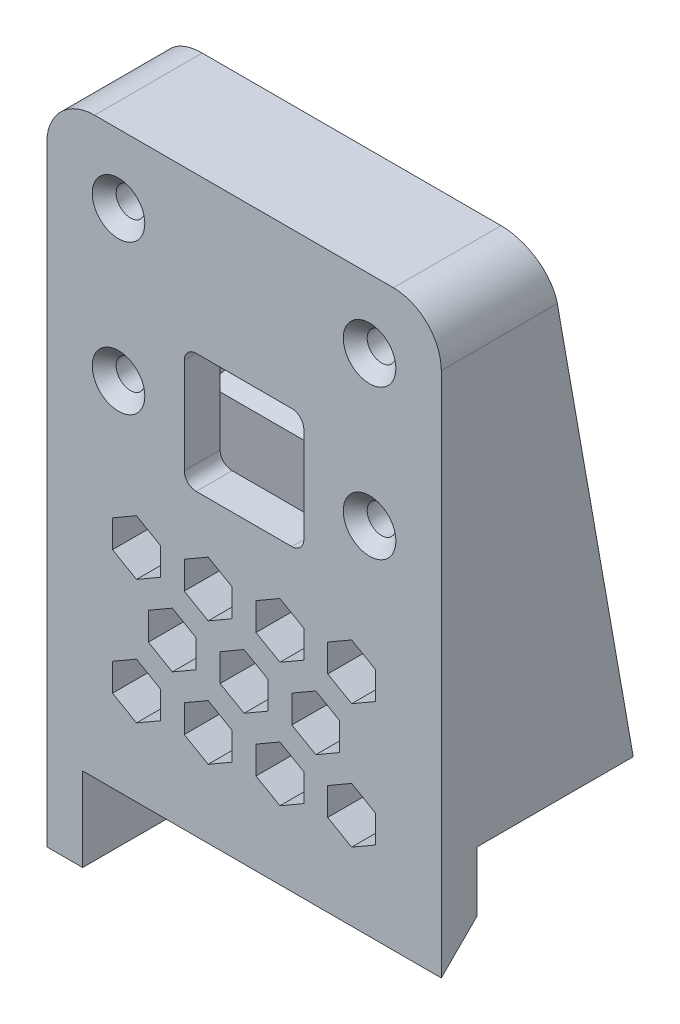
SolidWorks part; units mm, degrees
material "ABS PC"
ref_plane "Front Plane" through (0, 0, 0) normal (0, 0, 1) x (1, 0, 0)
ref_plane "Top Plane" through (0, 0, 0) normal (0, 1, 0) x (1, 0, 0)
ref_plane "Right Plane" through (0, 0, 0) normal (1, 0, 0) x (0, 0, -1)
sketch "Sketch1" plane through (0, 0, 0) normal (0, 0, 1) x (1, 0, 0)
  line L1 (16.5, -20) -> (-16.5, -20)
  line L2 (16.5, -20) -> (16.5, 20)
  line L3 (16.5, 20) -> (-16.5, 20)
  line L4 (-16.5, -20) -> (-16.5, 20)
  line L5 (16.5, -20) -> (-16.5, 20) construction
  line L6 (16.5, 20) -> (-16.5, -20) construction
  point P0 (0, 0)
  dimension "D1" = 33
  dimension "D2" = 40
extrude "Boss-Extrude1" add sketch "Sketch1" against normal blind 3
sketch "Sketch2" plane through (0, 0, -3) normal (0, 0, -1) x (-1, 0, 0)
  line L9 (13.5, -17) -> (13.5, 17)
  line L10 (13.5, 17) -> (-13.5, 17)
  line L11 (-13.5, 17) -> (-13.5, -17)
  line L12 (-13.5, -17) -> (13.5, -17)
  line L13 (13.5, -17) -> (13.5, 17)
  line L14 (13.5, 17) -> (-13.5, 17)
  line L15 (-13.5, 17) -> (-13.5, -17)
  line L16 (-13.5, -17) -> (13.5, -17)
  line L22 (16.5, -20) -> (16.5, 20)
  line L23 (16.5, 20) -> (-16.5, 20)
  line L24 (-16.5, 20) -> (-16.5, -20)
  line L25 (-16.5, -20) -> (16.5, -20)
  line L26 (16.5, -20) -> (16.5, 20)
  line L27 (16.5, 20) -> (-16.5, 20)
  line L28 (-16.5, 20) -> (-16.5, -20)
  line L29 (-16.5, -20) -> (16.5, -20)
  dimension "D1" = 3
  dimension "D2" = 0
extrude "Boss-Extrude2" add sketch "Sketch2" along normal blind 3
sketch "Sketch3" plane through (0, 0, 0) normal (0, 0, 1) x (1, 0, 0)
  line L0 (0, -20) -> (0, 2) construction
  line L1 (-16.5, -20) -> (16.5, -20) construction
  line L3 (-5, -3) -> (5, -3)
  line L4 (-5, -3) -> (-5, 7)
  line L5 (-5, 7) -> (5, 7)
  line L6 (5, -3) -> (5, 7)
  line L7 (-5, -3) -> (5, 7) construction
  line L8 (-5, 7) -> (5, -3) construction
  dimension "D1" = 10
  dimension "D2" = 22
extrude "Cut-Extrude1" cut sketch "Sketch3" against normal blind 3
hole_wizard "CSK for M2 Flat Head Machine Screw1" positions "Sketch9" profile "Sketch10" countersink size "M2" standard "ANSI Metric"
sketch "Sketch9" plane through (0, 0, 0) normal (0, 0, 1) x (1, 0, 0)
  line L0 (0, 0) -> (0, 8) construction
  line L3 (-10.5, 1.75) -> (10.5, 1.75)
  line L4 (-10.5, 1.75) -> (-10.5, 14.25)
  line L5 (-10.5, 14.25) -> (10.5, 14.25)
  line L6 (10.5, 1.75) -> (10.5, 14.25)
  line L7 (-10.5, 1.75) -> (10.5, 14.25) construction
  line L8 (-10.5, 14.25) -> (10.5, 1.75) construction
  point P5 (10.5, 14.25)
  point P8 (-10.5, 1.75)
  point P9 (-10.5, 14.25)
  point P10 (10.5, 1.75)
  dimension "D1" = 12.5
  dimension "D2" = 21
  dimension "D3" = 8
sketch "Sketch10" plane through (10.5, 1.75, 0) normal (1, 0, 0) x (0, -1, 0)
  line L0 (0, 0) -> (0, 5.721)
  line L1 (0, 5.721) -> (1.2, 5)
  line L2 (1.2, 5) -> (1.2, 1)
  line L3 (1.2, 1) -> (2.2, 0)
  line L5 (2.2, 0) -> (0, 0)
  line L6 (-1.2, 1) -> (-2.2, 0) construction
  line L10 (0, 5.721) -> (-1.2, 5) construction
  line L11 (0, -6.35) -> (0, 107.95) construction
  dimension "Hole Dia." = 2.4
  dimension "Hole Depth" = 5
  dimension "Near C'Sink Dia." = 4.4
  dimension "Near C'Sink Angle" = 90
  dimension "Drill Angle" = 118
sketch "Sketch11" plane through (-16.5, 0, 0) normal (-1, 0, 0) x (0, 0, 1)
  line L0 (-6, 20) -> (-9, 20)
  line L1 (-9, 20) -> (-16.0531, -20)
  line L2 (-16.0531, -20) -> (-6, -20)
  line L4 (-6, -20) -> (-6, 20)
  dimension "D1" = 3
  dimension "D2" = 10
extrude "Boss-Extrude4" add sketch "Sketch11" against normal blind 3
hole_wizard "Ø3.5 (3.5) Diameter Hole1" [suppressed] positions "Sketch12" profile "Sketch13" hole size "Ø3.5" standard "ANSI Metric"
sketch "Sketch12" plane through (-16.5, 0, 0) normal (-1, 0, 0) x (0, 0, 1)
  line L0 (-8.0249, -7.4838) -> (-8.9122, -12.5162) construction
  line L2 (-8, 20) -> (-15.0531, -20) construction
  line L3 (-12.4686, -10) -> (-8.4686, -10) construction
  line L4 (-15.0531, -20) -> (0, -20) construction
  point P0 (-8.0249, -7.4838)
  point P1 (-8.9122, -12.5162)
  dimension "D1" = 5.11
  dimension "D2" = 4
  dimension "D3" = 10
sketch "Sketch13" plane through (-16.5, -7.4838, -8.0249) normal (0, 1, 0) x (0, 0, 1)
  line L0 (0, 0) -> (0, 6.0515)
  line L1 (0, 6.0515) -> (1.75, 5)
  line L2 (1.75, 5) -> (1.75, 0)
  line L5 (1.75, 0) -> (0, 0)
  line L10 (0, 6.0515) -> (-1.75, 5) construction
  line L11 (0, -6.35) -> (0, 107.95) construction
  dimension "Hole Dia." = 3.5
  dimension "Hole Depth" = 5
  dimension "Drill Angle" = 118
mirror "Mirror1" about plane through (0, 0, 0) normal (1, 0, 0) of "Boss-Extrude4"
fillet "Fillet1" radius 1 4 edges at (-5, -3, -1.5) (5, -3, -1.5) (-5, 7, -1.5) (5, 7, -1.5)
sketch "Sketch15" plane through (0, 0, -6) normal (0, 0, -1) x (-1, 0, 0)
  line L1 (-13.5, 17) -> (13.5, 17)
  line L2 (-13.5, 17) -> (-13.5, 20)
  line L3 (-13.5, 20) -> (13.5, 20)
  line L4 (13.5, 17) -> (13.5, 20)
extrude "Boss-Extrude5" add sketch "Sketch15" along normal up to surface (3.529 mm away) up to face at (15, 0, -12.5265)
sketch "Sketch16" plane through (0, -20, 0) normal (0, -1, 0) x (1, 0, 0)
  line L0 (13.5, -9.529) -> (13.5, -3) construction
  line L1 (-13.5, -6) -> (13.5, -6)
  line L2 (-13.5, -6) -> (-13.5, -3)
  line L3 (-13.5, -3) -> (13.5, -3)
  line L4 (13.5, -6) -> (13.5, -3)
  line L5 (13.5, -6) -> (-13.5, -6) construction
  line L6 (-16.5, 0) -> (16.5, 0) construction
  dimension "D1" = 3
extrude "Cut-Extrude6" cut sketch "Sketch16" against normal blind 3 contours L3 L4 L1 L2
sketch "Sketch17" [suppressed] plane through (16.5, 0, 0) normal (1, 0, 0) x (0, 0, -1)
  line L0 (8.0249, -7.4838) -> (8.9122, -12.5162) construction
  circle A0 centre (8.4686, -10) radius 3
  dimension "D1" = 6
extrude "Cut-Extrude7" [suppressed] cut sketch "Sketch17" against normal blind 3
sketch "Sketch18" plane through (0, 2.1422, -12.1488) normal (0, 0.1736, -0.9848) x (-1, 0, 0)
  line L0 (13.5, 15.087) -> (-13.5, 15.087) construction
  line L1 (-13.5, -16.913) -> (13.5, -16.913)
  line L2 (-13.5, -16.913) -> (-13.5, -6.913)
  line L3 (-13.5, -6.913) -> (13.5, -6.913)
  line L4 (13.5, -16.913) -> (13.5, -6.913)
  line L7 (-13.5, 15.087) -> (-13.5, -22.4837) construction
  line L8 (13.5, 15.087) -> (13.5, -22.4837) construction
  dimension "D1" = 10
  dimension "D2" = 22
extrude "Boss-Extrude6" add sketch "Sketch18" against normal blind 3
sketch "Sketch19" plane through (0, 0, 0) normal (0, 0, 1) x (1, 0, 0)
  line L1 (-16.5, -20) -> (16.5, -20)
  line L2 (-16.5, -20) -> (-16.5, -24.0275)
  line L3 (-16.5, -24.0275) -> (16.5, -24.0275)
  line L4 (16.5, -20) -> (16.5, -24.0275)
extrude "Cut-Extrude8" [suppressed] cut sketch "Sketch19" against normal through all
chamfer "Chamfer4" [suppressed] distance 2 angle 45
sketch "Sketch20" [suppressed] plane through (-16.5, 0, 0) normal (-1, 0, 0) x (0, 0, 1)
  line L0 (-8.0249, -7.4838) -> (-8.9122, -12.5162) construction
  line L1 (-8.9122, -12.5162) -> (-8.0249, -7.4838) construction
  line L2 (-10.6357, -12.2123) -> (-9.7483, -7.1799)
  line L3 (-7.1888, -12.8201) -> (-6.3015, -7.7877)
  arc A0 (-10.6357, -12.2123) -> (-7.1888, -12.8201) centre (-8.9122, -12.5162) ccw
  arc A1 (-6.3015, -7.7877) -> (-9.7483, -7.1799) centre (-8.0249, -7.4838) ccw
  circle A2 centre (-8.0249, -7.4838) radius 1.75 construction
  point P5 (-8.4686, -10)
extrude "Cut-Extrude9" [suppressed] cut sketch "Sketch20" against normal blind 3
fillet "Fillet2" radius 4 2 edges at (16.5, 20, -4.5) (-16.5, 20, -4.5)
fillet "Fillet3" radius 2 2 edges at (-13.5, 17, -6.2645) (13.5, 17, -6.2645)
sketch "Sketch21" plane through (-16.5, 0, 0) normal (-1, 0, 0) x (0, 0, 1)
  line L1 (-16.0531, -20) -> (0, -20)
  line L2 (-16.0531, -20) -> (-16.0531, -35)
  line L3 (-16.0531, -35) -> (0, -35)
  line L4 (0, -20) -> (0, -35)
  dimension "D1" = 15
extrude "Boss-Extrude7" add sketch "Sketch21" against normal up to surface (3 mm away) up to face at (-13.5, -6.1751, -10.362)
sketch "Sketch22" plane through (-16.5, 0, 0) normal (-1, 0, 0) x (0, 0, 1)
  line L0 (-8.0265, -29.555) -> (-8.0265, -24.445) construction
  line L1 (-9.5265, -29.555) -> (-9.5265, -24.445)
  line L2 (-6.5265, -29.555) -> (-6.5265, -24.445)
  line L3 (-8.0265, -29.555) -> (-8.0265, -35) construction
  line L4 (-16.0531, -35) -> (0, -35) construction
  arc A0 (-9.5265, -29.555) -> (-6.5265, -29.555) centre (-8.0265, -29.555) ccw
  arc A1 (-6.5265, -24.445) -> (-9.5265, -24.445) centre (-8.0265, -24.445) ccw
  point P2 (-8.0265, -27)
  dimension "D1" = 5.11
  dimension "D2" = 8
  dimension "D3" = 3
extrude "Cut-Extrude10" cut sketch "Sketch22" against normal blind 10
sketch "Sketch23" plane through (0, 0, 0) normal (0, 0, 1) x (1, 0, 0)
  line L1 (-13.5, -20) -> (16.5, -20)
  line L2 (-13.5, -20) -> (-13.5, -28)
  line L3 (-13.5, -28) -> (16.5, -28)
  line L4 (16.5, -20) -> (16.5, -28)
  dimension "D1" = 8
extrude "Boss-Extrude8" add sketch "Sketch23" against normal blind 3
chamfer "Chamfer5" distance 3 angle 45 1 edges at (1.5, -28, -3)
sketch "Sketch24" plane through (0, 0, 0) normal (0, 0, 1) x (1, 0, 0)
  line L0 (0, -10.5048) -> (0, -23.4952) construction
  line L1 (0, -10.5048) -> (-7.5, -23.4952)
  line L2 (-7.5, -23.4952) -> (7.5, -23.4952)
  line L3 (0, -10.5048) -> (7.5, -23.4952)
  point P6 (0, -17)
  dimension "D1" = 15
  dimension "D2" = 17
extrude "Cut-Extrude11" [suppressed] cut sketch "Sketch24" against normal blind 3
fillet "Fillet4" [suppressed] radius 2
chamfer "Chamfer6" distance 1 angle 45 4 edges at (-16.5, -27, -6.5265) (-16.5, -22.945, -8.0265) (-16.5, -31.055, -8.0265) (-16.5, -27, -9.5265)
sketch "Sketch25" plane through (0, 0, 0) normal (0, 0, 1) x (1, 0, 0)
  line L0 (0, -9.5695) -> (0, -22.3789) construction
  line L1 (-1, -8.4148) -> (-3, -7.2601)
  line L2 (-7, -8.4148) -> (-9, -7.2601)
  line L3 (-9, -7.2601) -> (-11, -8.4148)
  line L4 (-11, -8.4148) -> (-11, -10.7242)
  line L5 (-11, -10.7242) -> (-9, -11.8789)
  line L6 (-9, -11.8789) -> (-7, -10.7242)
  line L7 (-7, -10.7242) -> (-7, -8.4148)
  line L8 (-3, -7.2601) -> (-5, -8.4148)
  line L9 (-5, -8.4148) -> (-5, -10.7242)
  line L10 (-5, -10.7242) -> (-3, -11.8789)
  line L11 (-3, -11.8789) -> (-1, -10.7242)
  line L12 (-1, -10.7242) -> (-1, -8.4148)
  line L13 (1, -10.7242) -> (1, -8.4148)
  line L14 (3, -11.8789) -> (1, -10.7242)
  line L15 (5, -10.7242) -> (3, -11.8789)
  line L16 (5, -8.4148) -> (5, -10.7242)
  line L17 (3, -7.2601) -> (5, -8.4148)
  line L18 (7, -10.7242) -> (7, -8.4148)
  line L19 (9, -11.8789) -> (7, -10.7242)
  line L20 (11, -10.7242) -> (9, -11.8789)
  line L21 (11, -8.4148) -> (11, -10.7242)
  line L22 (9, -7.2601) -> (11, -8.4148)
  line L23 (7, -8.4148) -> (9, -7.2601)
  line L24 (1, -8.4148) -> (3, -7.2601)
  line L25 (-3, -9.5695) -> (-9, -9.5695) construction
  line L26 (0, -12.4563) -> (-2, -13.611)
  line L27 (-6, -12.4563) -> (-8, -13.611)
  line L28 (-8, -13.611) -> (-8, -15.9204)
  line L29 (-8, -15.9204) -> (-6, -17.0751)
  line L30 (-6, -17.0751) -> (-4, -15.9204)
  line L31 (-4, -15.9204) -> (-4, -13.611)
  line L32 (-4, -13.611) -> (-6, -12.4563)
  line L33 (-2, -13.611) -> (-2, -15.9204)
  line L34 (-2, -15.9204) -> (0, -17.0751)
  line L35 (0, -17.0751) -> (2, -15.9204)
  line L36 (2, -15.9204) -> (2, -13.611)
  line L37 (2, -13.611) -> (0, -12.4563)
  line L38 (6, -12.4563) -> (4, -13.611)
  line L39 (4, -13.611) -> (4, -15.9204)
  line L40 (4, -15.9204) -> (6, -17.0751)
  line L41 (6, -17.0751) -> (8, -15.9204)
  line L42 (8, -15.9204) -> (8, -13.611)
  line L43 (8, -13.611) -> (6, -12.4563)
  line L44 (-3, -14.7657) -> (3, -14.7657) construction
  line L45 (-3, -19.9618) -> (-9, -19.9618) construction
  line L46 (1, -21.1165) -> (3, -22.2712)
  line L47 (7, -21.1165) -> (9, -22.2712)
  line L48 (9, -22.2712) -> (11, -21.1165)
  line L49 (11, -21.1165) -> (11, -18.8071)
  line L50 (11, -18.8071) -> (9, -17.6524)
  line L51 (9, -17.6524) -> (7, -18.8071)
  line L52 (7, -18.8071) -> (7, -21.1165)
  line L53 (3, -22.2712) -> (5, -21.1165)
  line L54 (5, -21.1165) -> (5, -18.8071)
  line L55 (5, -18.8071) -> (3, -17.6524)
  line L56 (3, -17.6524) -> (1, -18.8071)
  line L57 (1, -18.8071) -> (1, -21.1165)
  line L58 (-1, -18.8071) -> (-1, -21.1165)
  line L59 (-3, -17.6524) -> (-1, -18.8071)
  line L60 (-5, -18.8071) -> (-3, -17.6524)
  line L61 (-5, -21.1165) -> (-5, -18.8071)
  line L62 (-3, -22.2712) -> (-5, -21.1165)
  line L63 (-7, -18.8071) -> (-7, -21.1165)
  line L64 (-9, -17.6524) -> (-7, -18.8071)
  line L65 (-11, -18.8071) -> (-9, -17.6524)
  line L66 (-11, -21.1165) -> (-11, -18.8071)
  line L67 (-9, -22.2712) -> (-11, -21.1165)
  line L68 (-7, -21.1165) -> (-9, -22.2712)
  line L69 (-1, -21.1165) -> (-3, -22.2712)
  circle A0 centre (-9, -9.5695) radius 2 construction
  circle A1 centre (-3, -9.5695) radius 2 construction
  circle A2 centre (3, -9.5695) radius 2 construction
  circle A3 centre (9, -9.5695) radius 2 construction
  circle A4 centre (-6, -14.7657) radius 2 construction
  circle A5 centre (0, -14.7657) radius 2 construction
  circle A6 centre (6, -14.7657) radius 2 construction
  circle A7 centre (9, -19.9618) radius 2 construction
  circle A8 centre (3, -19.9618) radius 2 construction
  circle A9 centre (-3, -19.9618) radius 2 construction
  circle A10 centre (-9, -19.9618) radius 2 construction
  point P40 (-6, -9.5695)
  point P94 (-6, -19.9618)
  dimension "D1" = 4
  dimension "D3" = 6
  dimension "D4" = 6
  dimension "D5" = 2
  dimension "D6" = 2
  dimension "D7" = 2
  dimension "D2" = 2
  dimension "D8" = 3
extrude "Cut-Extrude12" cut sketch "Sketch25" against normal blind 10
